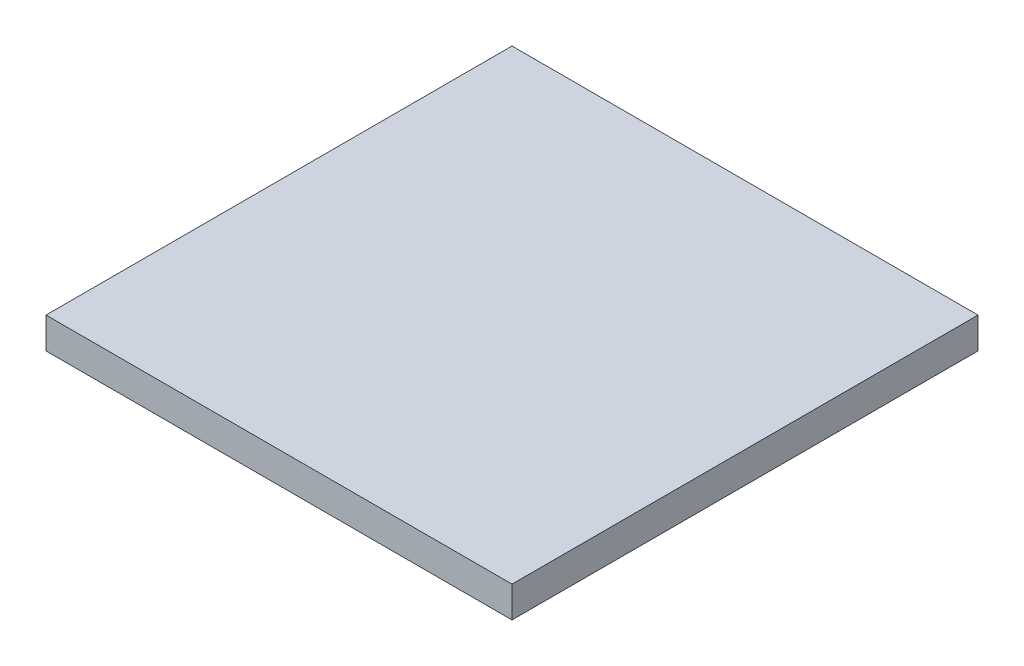
SolidWorks part; units mm, degrees
ref_plane "Front Plane" through (0, 0, 0) normal (0, 0, 1) x (1, 0, 0)
ref_plane "Top Plane" through (0, 0, 0) normal (0, 1, 0) x (1, 0, 0)
ref_plane "Right Plane" through (0, 0, 0) normal (1, 0, 0) x (0, 0, -1)
sketch "Sketch1" plane through (0, 0, 0) normal (0, 1, 0) x (1, 0, 0)
  line L1 (-19.05, -19.05) -> (19.05, -19.05)
  line L2 (-19.05, -19.05) -> (-19.05, 19.05)
  line L3 (-19.05, 19.05) -> (19.05, 19.05)
  line L4 (19.05, -19.05) -> (19.05, 19.05)
  line L5 (-19.05, -19.05) -> (19.05, 19.05) construction
  line L6 (-19.05, 19.05) -> (19.05, -19.05) construction
  point P0 (0, 0)
  dimension "D1" = 38.1
  dimension "D2" = 38.1
extrude "Boss-Extrude1" add sketch "Sketch1" along normal blind 2.54
